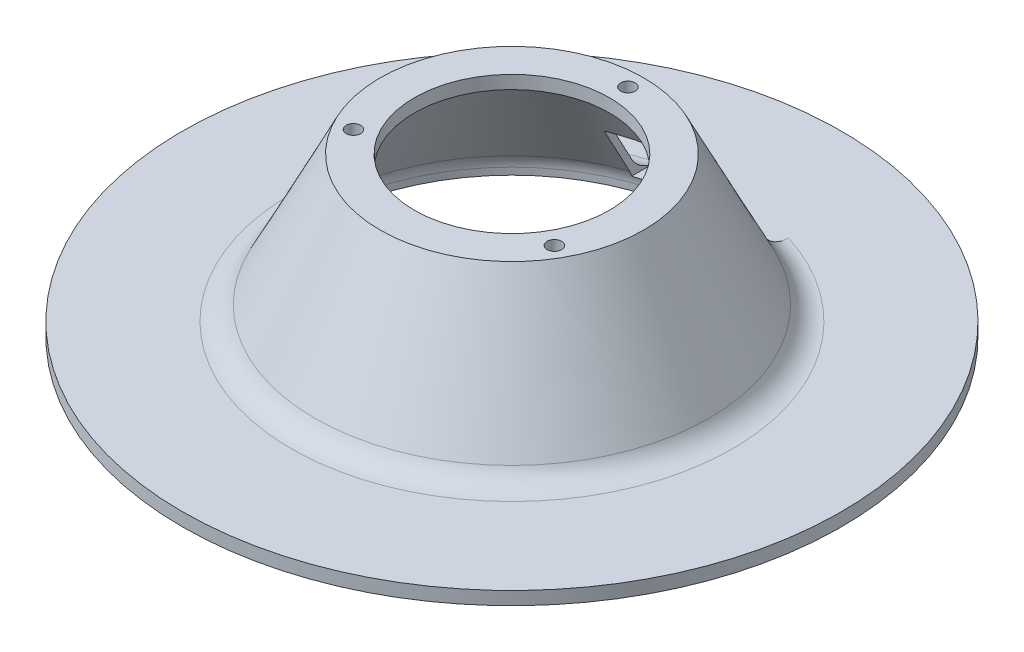
SolidWorks part; units mm, degrees
ref_plane "Front Plane" through (0, 0, 0) normal (0, 0, 1) x (1, 0, 0)
ref_plane "Top Plane" through (0, 0, 0) normal (0, 1, 0) x (1, 0, 0)
ref_plane "Right Plane" through (0, 0, 0) normal (1, 0, 0) x (0, 0, -1)
sketch "Sketch1" plane through (0, 0, 0) normal (0, 1, 0) x (1, 0, 0)
  circle A0 centre (0, 0) radius 44 construction
  circle A1 centre (0, 44) radius 2.75
  circle A2 centre (38.1051, -22) radius 2.75
  circle A3 centre (-38.1051, -22) radius 2.75
  circle A4 centre (0, 0) radius 37
  circle A5 centre (0, 0) radius 50
  point P11 (0, 0)
  dimension "D1" = 88
  dimension "D3" = 5.5
  dimension "D4" = 74
  dimension "D5" = 100
  dimension "D2" = 3
extrude "Boss-Extrude1" add sketch "Sketch1" along normal blind 5
ref_plane "Plane1" through (0, -55, 0) normal (0, 1, 0) x (1, 0, 0)
sketch "Sketch2" plane through (0, -55, 0) normal (0, 1, 0) x (1, 0, 0)
  circle A0 centre (0, 0) radius 125
  circle A1 centre (0, 0) radius 75
  dimension "D1" = 250
  dimension "D2" = 150
extrude "Boss-Extrude2" add sketch "Sketch2" along normal blind 5 separate body
sketch "Sketch3" plane through (0, 0, 0) normal (0, 0, 1) x (1, 0, 0)
  line L0 (-50, 0) -> (-75, -50)
  line L1 (-50, 5) -> (-77.5, -50)
  line L2 (-50, 5) -> (-50, 0)
  line L3 (-77.5, -50) -> (-75, -50)
  line L4 (0, 0) -> (0, -50) construction
revolve "Revolve1" add sketch "Sketch3" angle 360 about L4
fillet "Fillet1" radius 10 2 edges at (0, -50, 77.5) (0, -50, 75)
sketch "Sketch4" plane through (0, 0, 0) normal (0, 0, 1) x (1, 0, 0)
  line L1 (-25, -30) -> (25, -30)
  line L2 (-25, -30) -> (-25, -50)
  line L3 (-25, -50) -> (25, -50)
  line L4 (25, -30) -> (25, -50)
  line L5 (125, -50) -> (-125, -50) construction
  point P6 (0, -30)
  dimension "D1" = 50
  dimension "D2" = 20
extrude "Cut-Extrude1" cut sketch "Sketch4" against normal through all
